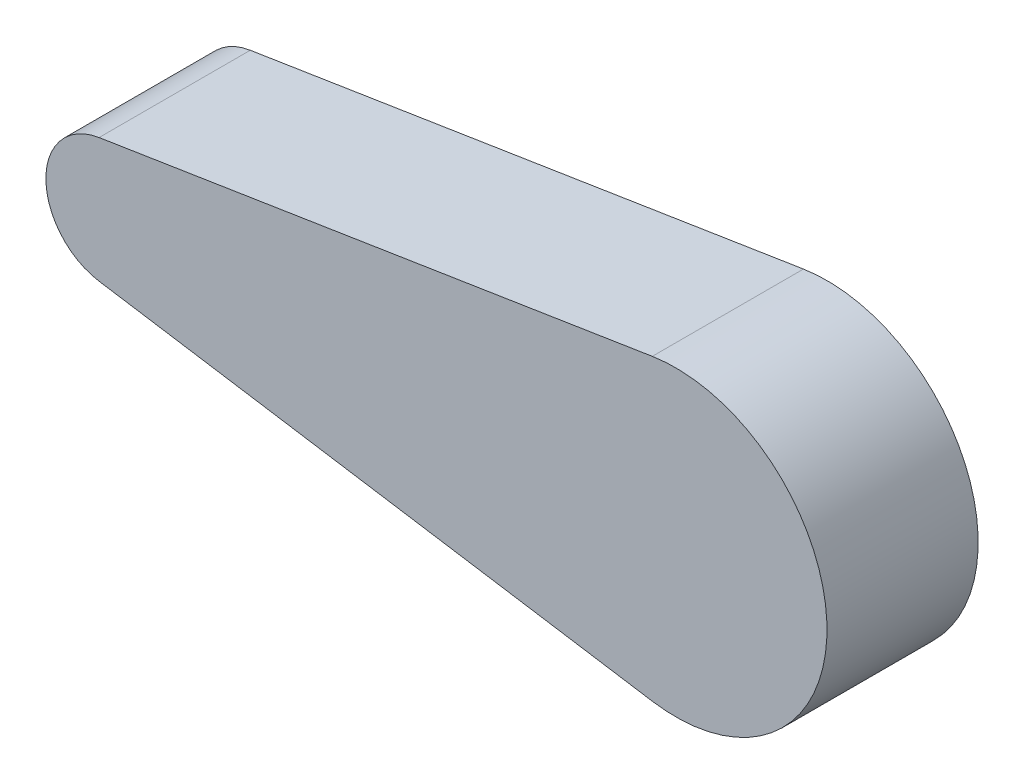
SolidWorks part; units mm, degrees
ref_plane "Top Plane" through (0, 0, 0) normal (0, 0, 1) x (1, 0, 0)
ref_plane "Right Plane" through (0, 0, 0) normal (0, 1, 0) x (1, 0, 0)
ref_plane "Front Plane" through (0, 0, 0) normal (1, 0, 0) x (0, 0, -1)
sketch "Sketch1" plane through (0, 0, 0) normal (0, 0, 1) x (1, 0, 0)
  line L0 (0, 0) -> (-22.5, 0) construction
  line L1 (-22.8889, -2.4696) -> (-0.9333, -5.927)
  line L3 (-22.8889, 2.4696) -> (-0.9333, 5.927)
  arc A0 (-0.9333, -5.927) -> (-0.9333, 5.927) centre (0, 0) ccw
  arc A1 (-22.8889, 2.4696) -> (-22.8889, -2.4696) centre (-22.5, 0) ccw
  point P1 (-25, 0)
  dimension "D1" = 12
  dimension "D2" = 5
  dimension "D3" = 25
extrude "Boss-Extrude1" add sketch "Sketch1" along normal blind 2
sketch "Sketch2" plane through (0, 0, 0) normal (0, 0, -1) x (-1, 0, 0)
  line L0 (14.05, 0) -> (0, 0) construction
  line L1 (14.1755, 2.2966) -> (2.3225, 2.9443)
  line L2 (2.2091, 2.65) -> (14.1591, 1.997) construction
  line L3 (14.1755, -2.2966) -> (2.3225, -2.9443)
  line L4 (14.1591, -1.997) -> (2.2091, -2.65) construction
  line L5 (2.2091, 2.65) -> (14.1591, 1.997) construction
  line L6 (14.1591, -1.997) -> (2.2091, -2.65) construction
  line L9 (22.8889, 2.4696) -> (0.9333, 5.927)
  line L10 (0.9333, -5.927) -> (22.8889, -2.4696)
  line L11 (22.8889, 2.4696) -> (0.9333, 5.927)
  line L12 (0.9333, -5.927) -> (22.8889, -2.4696)
  arc A0 (2.3225, 2.9443) -> (2.3225, -2.9443) centre (0, 0) ccw
  arc A1 (2.2091, 2.65) -> (2.2091, -2.65) centre (0, 0) ccw construction
  arc A2 (14.1755, -2.2966) -> (14.1755, 2.2966) centre (14.05, 0) ccw
  arc A3 (14.1591, -1.997) -> (14.1591, 1.997) centre (14.05, 0) ccw construction
  arc A4 (14.1591, -1.997) -> (14.1591, 1.997) centre (14.05, 0) ccw construction
  arc A7 (22.8889, -2.4696) -> (22.8889, 2.4696) centre (22.5, 0) ccw
  arc A8 (0.9333, 5.927) -> (0.9333, -5.927) centre (0, 0) ccw
  arc A9 (22.8889, -2.4696) -> (22.8889, 2.4696) centre (22.5, 0) ccw
  arc A10 (0.9333, 5.927) -> (0.9333, -5.927) centre (0, 0) ccw
  point P7 (0, 0)
  point P12 (0, 0)
  dimension "D1" = 0.3
  dimension "D2" = 0.3
  dimension "D3" = 0
extrude "Boss-Extrude2" add sketch "Sketch2" along normal blind 4
